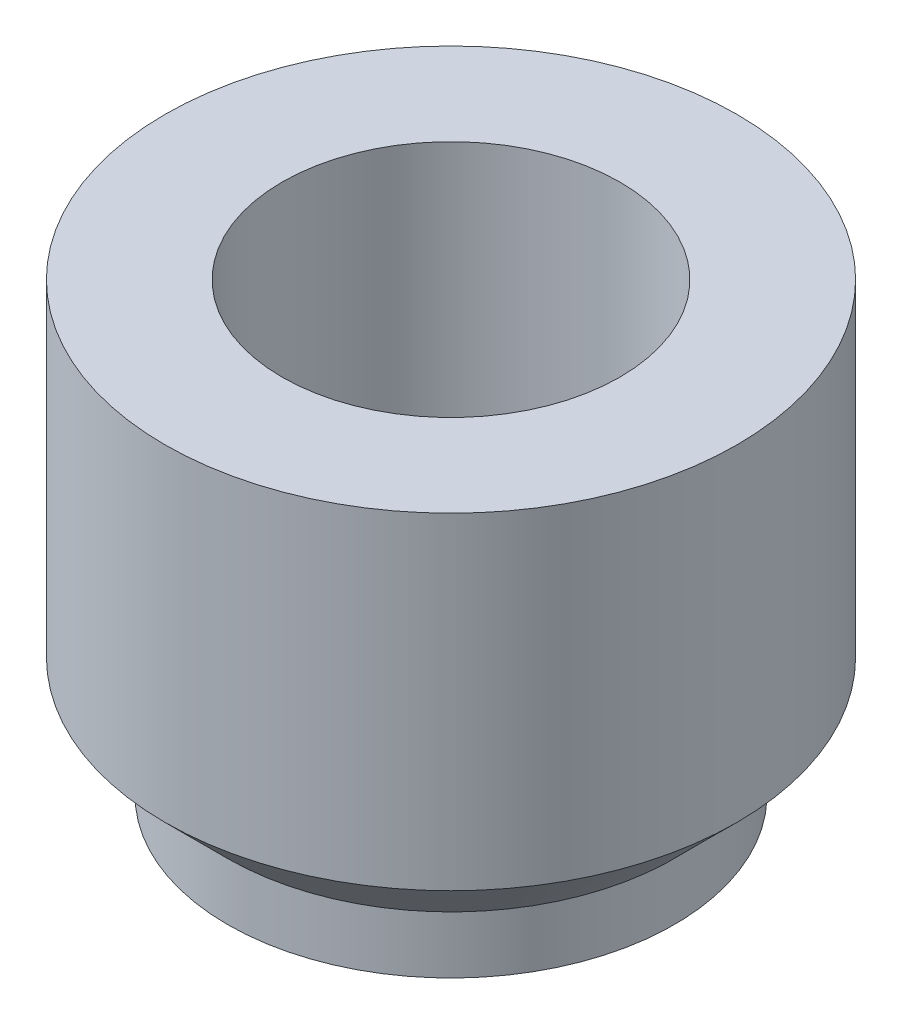
SolidWorks part; units mm, degrees
ref_plane "Front Plane" through (0, 0, 0) normal (0, 0, 1) x (1, 0, 0)
ref_plane "Top Plane" through (0, 0, 0) normal (0, 1, 0) x (1, 0, 0)
ref_plane "Right Plane" through (0, 0, 0) normal (1, 0, 0) x (0, 0, -1)
sketch "Sketch1" plane through (0, 0, 0) normal (0, 1, 0) x (1, 0, 0)
  circle A0 centre (0, 0) radius 2.1
  circle A1 centre (0, 0) radius 4.1
  dimension "D1" = 4.2
  dimension "D2" = 2
extrude "Boss-Extrude1" add sketch "Sketch1" along normal blind 2.2
sketch "Sketch2" plane through (0, 2.2, 0) normal (0, 1, 0) x (1, 0, 0)
  circle A0 centre (0, 0) radius 5.25
  dimension "D1" = 10.5
extrude "Boss-Extrude2" add sketch "Sketch2" along normal blind 1
sketch "Sketch3" plane through (0, 3.2, 0) normal (0, 1, 0) x (1, 0, 0)
  circle A0 centre (0, 0) radius 3.1
  circle A1 centre (0, 0) radius 5.25 construction
  circle A2 centre (0, 0) radius 5.25
  dimension "D1" = 6.2
extrude "Boss-Extrude3" add sketch "Sketch3" along normal blind 5
chamfer "Chamfer1" distance 1.15 angle 45 1 edges at (0, 2.2, 4.1)
